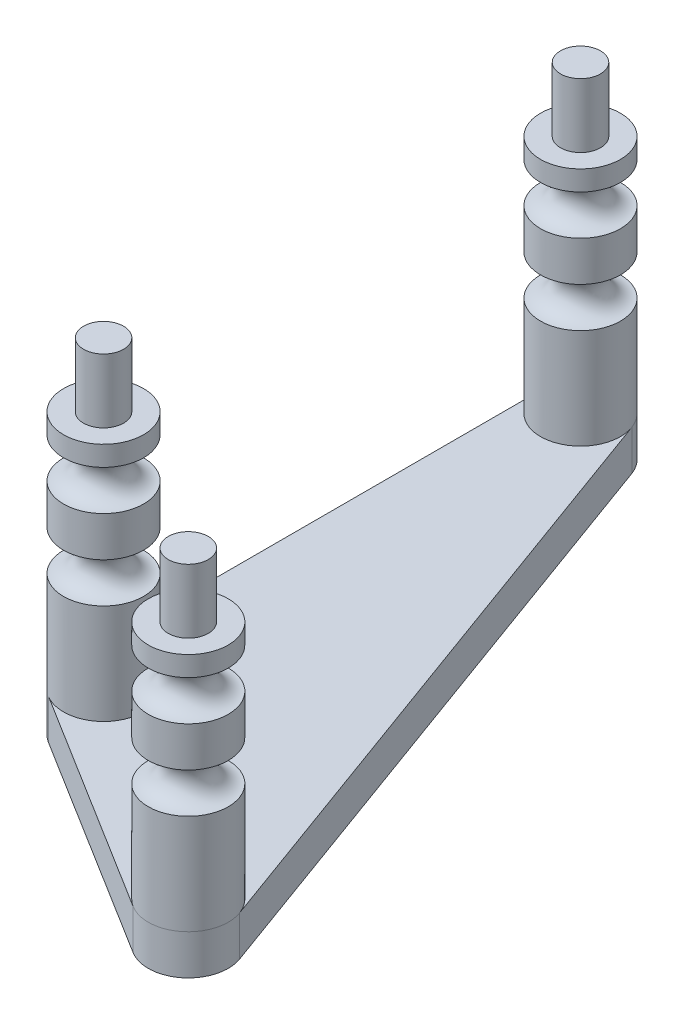
SolidWorks part; units mm, degrees
material "ABS"
ref_plane "Front Plane" through (0, 0, 0) normal (0, 0, 1) x (1, 0, 0)
ref_plane "Top Plane" through (0, 0, 0) normal (0, 1, 0) x (1, 0, 0)
ref_plane "Right Plane" through (0, 0, 0) normal (1, 0, 0) x (0, 0, -1)
sketch "Sketch1" plane through (0, 0, 0) normal (0, 1, 0) x (1, 0, 0)
  line L0 (0, 0) -> (0, 75.6844)
  line L1 (0, 75.6844) -> (35.6175, -22.1738)
  line L2 (35.6175, -22.1738) -> (0, 0)
  line L3 (-6.35, -3.5268) -> (-6.35, 111.697)
  line L4 (-6.35, 111.697) -> (47.8749, -37.2848)
  line L5 (47.8749, -37.2848) -> (-6.35, -3.5268)
  circle A0 centre (0, 75.6844) radius 6.35
  circle A1 centre (0, 0) radius 6.35
  circle A2 centre (35.6175, -22.1738) radius 6.35
  dimension "D5" = 12.7
  dimension "D6" = 12.7
  dimension "D7" = 12.7
  dimension "D1" = 20
  dimension "D2" = 75.6844
  dimension "D3" = 41.9557
  dimension "D4" = 6.35
extrude "Boss-Extrude1" add sketch "Sketch1" along normal blind 6.35 contours A2 L2 A1 L5 | A2 L5 L4 | A2 L4 A0 L1 | A1 L0 A0 L3 | A0 L4 L3 | A2 L1 A0 L0 A1 L2 | A2 | A1 | A0 region at (-3.2479, 0, -37.8422) region at (12.008, 0, -18.4658) region at (16.0516, 0, 13.9093) region at (-2.7233, 0, -91.1291) region at (20.84, 0, -27.8586) region at (41.9947, 0, 30.0357)
extrude "Boss-Extrude2" add sketch "Sketch1<4>" along normal blind 44.45 contours A0 | A1 | A2
sketch "Sketch1<4>" plane through (0, 0, 0) normal (0, 1, 0) x (1, 0, 0) same geometry as "Sketch1"
fillet "Fillet1" radius 6.35 2 edges at (47.8749, 3.175, 37.2848) (-6.35, 3.175, -111.697)
sketch "Sketch3" plane through (0, 44.45, 0) normal (0, 1, 0) x (1, 0, 0)
  circle A0 centre (0, 0) radius 3.175
  circle A1 centre (35.6175, -22.1738) radius 3.175
  circle A2 centre (0, 75.6844) radius 3.175
  dimension "D1" = 6.35
extrude "Boss-Extrude3" add sketch "Sketch3" along normal blind 10.16
ref_axis "Axis1" through (35.6175, 6.35, 22.1738) along (0, 1, 0)
ref_plane "Plane1" through (35.6175, 0, 22.1738) normal (0.8489, 0, 0.5285) x (0, 1, 0)
sketch "Sketch4" plane through (35.6175, 0, 22.1738) normal (0.8489, 0, 0.5285) x (0, 1, 0)
  line L1 (44.45, -6.35) -> (44.45, 6.35) construction
  circle A0 centre (38.1, 6.35) radius 3.175
  circle A1 centre (25.4, 6.35) radius 3.175
  dimension "D1" = 6.35
  dimension "D2" = 6.35
  dimension "D3" = 19.05
revolve "Cut-Revolve1" cut sketch "Sketch4" angle 360 about axis through (35.6175, 6.35, 22.1738) along (0, 1, 0)
ref_axis "Axis2" through (0, 6.35, 0) along (0, -1, 0)
ref_plane "Plane2" through (0, 0, 0) normal (-0.8489, 0, -0.5285) x (0, -1, 0)
sketch "Sketch5" plane through (0, 0, 0) normal (-0.8489, 0, -0.5285) x (0, -1, 0)
  line L1 (-44.45, 6.35) -> (-44.45, -6.35) construction
  circle A0 centre (-38.1, 6.35) radius 3.175
  circle A1 centre (-25.4, 6.35) radius 3.175
  dimension "D2" = 19.05
  dimension "D3" = 6.35
  dimension "D4" = 6.35
  dimension "D1" = 6.35
revolve "Cut-Revolve2" cut sketch "Sketch5" angle 360 about axis through (0, 6.35, 0) along (0, -1, 0)
ref_axis "Axis3" through (0, 6.35, -75.6844) along (0, 1, 0)
ref_plane "Plane3" through (-24.3245, 0, -66.831) normal (-0.342, 0, -0.9397) x (0, 1, 0)
sketch "Sketch6" plane through (-24.3245, 0, -66.831) normal (-0.342, 0, -0.9397) x (0, 1, 0)
  line L0 (44.45, 32.2356) -> (6.35, 32.2356) construction
  line L1 (44.45, 32.2356) -> (6.35, 32.2356) construction
  line L2 (44.45, 19.5356) -> (44.45, 32.2356) construction
  circle A0 centre (38.1, 32.2356) radius 3.175
  circle A1 centre (25.4, 32.2356) radius 3.175
  dimension "D1" = 6.35
  dimension "D2" = 19.05
  dimension "D3" = 6.35
  dimension "D4" = 6.35
revolve "Cut-Revolve3" cut sketch "Sketch6" angle 360 about axis through (0, 6.35, -75.6844) along (0, 1, 0)
